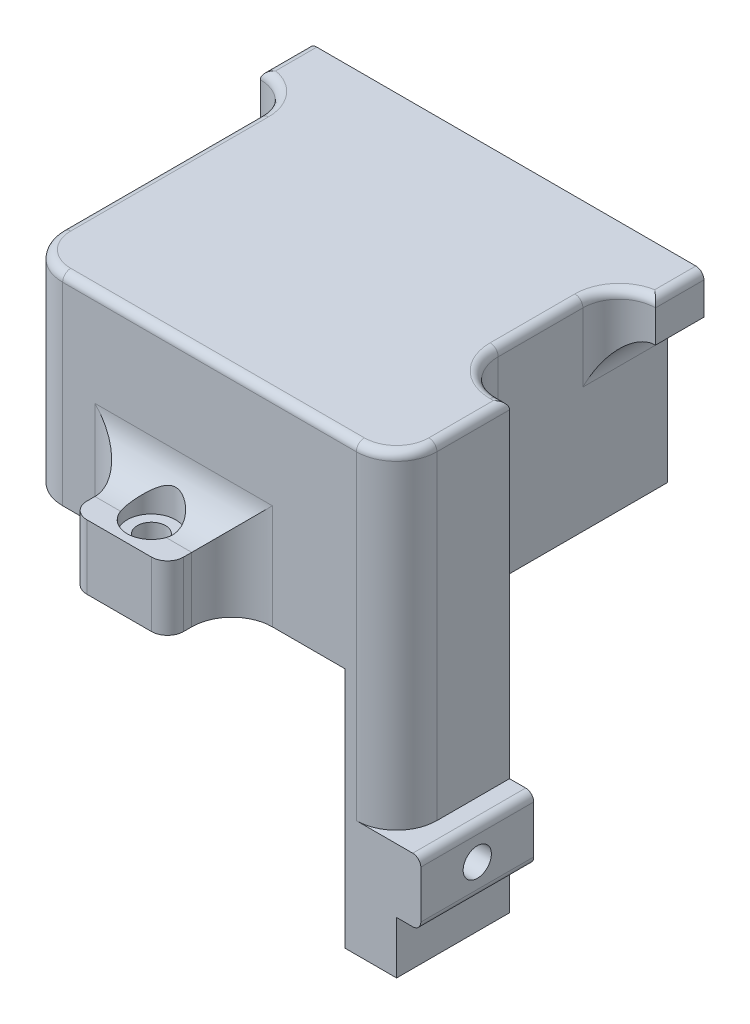
SolidWorks part; units mm, degrees
ref_plane "Alzado" through (0, 0, 0) normal (0, 0, 1) x (1, 0, 0)
ref_plane "Planta" through (0, 0, 0) normal (0, 1, 0) x (1, 0, 0)
ref_plane "Vista lateral" through (0, 0, 0) normal (1, 0, 0) x (0, 0, -1)
sketch "Croquis1" plane through (0, 0, 0) normal (0, 1, 0) x (1, 0, 0)
  line L1 (0, 0) -> (40, 0)
  line L2 (0, 0) -> (0, -40)
  line L3 (0, -40) -> (40, -40)
  line L4 (40, 0) -> (40, -40)
  dimension "D1" = 40
  dimension "D2" = 40
extrude "Saliente-Extruir1" add sketch "Croquis1" along normal blind 25
sketch "Croquis3" plane through (0, 0, 0) normal (0, 0, -1) x (-1, 0, 0)
  line L0 (0, 0) -> (-40, 25) construction
  line L1 (-40, 25) -> (0, 25) construction
  line L2 (-40, 25) -> (-40, 0) construction
  line L4 (-5, 21.5) -> (-35, 21.5)
  line L5 (-5, 21.5) -> (-5, 3.5)
  line L6 (-5, 3.5) -> (-35, 3.5)
  line L7 (-35, 21.5) -> (-35, 3.5)
  line L8 (-5, 21.5) -> (-35, 3.5) construction
  line L9 (-5, 3.5) -> (-35, 21.5) construction
  point P7 (-20, 12.5)
  dimension "D1" = 30
  dimension "D2" = 18
extrude "Cortar-Extruir1" cut sketch "Croquis3" against normal blind 30
sketch "Croquis4" plane through (0, 25, 0) normal (0, 1, 0) x (1, 0, 0)
  line L0 (40, -40) -> (40, 0) construction
  line L1 (35.5, 4) -> (44.5, 4)
  line L2 (35.5, 4) -> (35.5, -6)
  line L3 (35.5, -6) -> (44.5, -6)
  line L4 (44.5, 4) -> (44.5, -6)
  line L5 (4.5, 4) -> (-4.5, 4)
  line L6 (4.5, 4) -> (4.5, -6)
  line L7 (4.5, -6) -> (-4.5, -6)
  line L8 (-4.5, 4) -> (-4.5, -6)
  line L9 (40, 0) -> (0, 0) construction
  line L10 (0, 0) -> (0, -40) construction
  dimension "D1" = 9
  dimension "D2" = 4.5
  dimension "D3" = 10
  dimension "D4" = 4
  dimension "D5" = 9
  dimension "D6" = 10
  dimension "D7" = 4.5
  dimension "D8" = 4
extrude "Saliente-Extruir2" add sketch "Croquis4" against normal blind 5
fillet "Redondeo3" radius 4.5 4 edges at (0, 22.5, 6) (40, 22.5, 6) (0, 20, 3) (40, 20, 3)
sketch "Croquis8" plane through (0, 25, 0) normal (0, 1, 0) x (1, 0, 0)
  line L0 (40, -40) -> (40, -10.5) construction
  line L1 (40, -26) -> (46.4, -26)
  line L2 (40, -26) -> (40, -40)
  line L3 (40, -40) -> (46.4, -40)
  line L4 (46.4, -26) -> (46.4, -40)
  line L5 (0, -40) -> (40, -40) construction
  dimension "D1" = 6.4
  dimension "D2" = 14
extrude "Saliente-Extruir5" add sketch "Croquis8" against normal blind 55
sketch "Croquis9" plane through (46.4, 0, 0) normal (1, 0, 0) x (0, 0, -1)
  line L0 (-26, -30) -> (-26, 25) construction
  line L1 (-26, -15.6) -> (-40, -15.6)
  line L2 (-26, -15.6) -> (-26, -23.5)
  line L3 (-26, -23.5) -> (-40, -23.5)
  line L4 (-40, -15.6) -> (-40, -23.5)
  line L5 (-40, -30) -> (-40, 25) construction
  line L6 (-40, -30) -> (-26, -30) construction
  dimension "D1" = 7.9
  dimension "D2" = 6.5
extrude "Saliente-Extruir6" add sketch "Croquis9" along normal blind 3
sketch "Croquis10" plane through (0, 0, 0) normal (0, -1, 0) x (1, 0, 0)
  line L5 (20, 0) -> (20, 40) construction
  line L6 (0, 10.5) -> (-8, 10.5)
  line L7 (0, 10.5) -> (0, 22.5)
  line L8 (0, 22.5) -> (-8, 22.5)
  line L9 (-8, 10.5) -> (-8, 22.5)
  line L10 (40, 0) -> (0, 0) construction
  line L11 (0, 40) -> (40, 40) construction
  line L13 (26, 40) -> (14, 40)
  line L14 (26, 40) -> (26, 48)
  line L15 (26, 48) -> (14, 48)
  line L16 (14, 40) -> (14, 48)
  dimension "D1" = 12
  dimension "D2" = 8
  dimension "D3" = 12
  dimension "D4" = 8
  dimension "D5" = 6
extrude "Saliente-Extruir7" add sketch "Croquis10" against normal blind 8
sketch "Croquis11" plane through (0, 0, 0) normal (0, -1, 0) x (1, 0, 0)
  line L0 (-8, 16.5) -> (0.4912, 16.5) construction
  line L1 (-8, 22.5) -> (-8, 10.5) construction
  line L2 (-4, 10.5) -> (-4, 22.5) construction
  line L5 (26, 44) -> (14, 44) construction
  line L6 (26, 40) -> (26, 48) construction
  line L7 (14, 48) -> (14, 40) construction
  line L8 (20, 48) -> (20, 39.7958) construction
  line L9 (26, 48) -> (14, 48) construction
  line L10 (-8, 10.5) -> (0, 10.5) construction
  line L11 (0, 22.5) -> (-8, 22.5) construction
  circle A0 centre (20, 44) radius 1.75
  circle A1 centre (-4, 16.5) radius 1.75
  dimension "D1" = 3.5
  dimension "D2" = 3.5
extrude "Cortar-Extruir2" cut sketch "Croquis11" against normal up to surface (8 mm away) up to face at (-4, 8, 16.5)
sketch "Croquis12" plane through (0, 8, 0) normal (0, 1, 0) x (1, 0, 0)
  circle A0 centre (20, -44) radius 3
  circle A1 centre (-4, -16.5) radius 3
  dimension "D1" = 6
  dimension "D2" = 6
extrude "Cortar-Extruir3" cut sketch "Croquis12" against normal blind 1.5
fillet "Redondeo5" radius 1 2 edges at (49.4, -15.6, 33) (49.4, -23.5, 33)
sketch "Croquis13" plane through (49.4, 0, 0) normal (1, 0, 0) x (0, 0, -1)
  line L0 (-26, -19.55) -> (-40, -19.55) construction
  line L1 (-26, -22.5) -> (-26, -16.6) construction
  line L2 (-40, -16.6) -> (-40, -22.5) construction
  circle A0 centre (-33, -19.55) radius 1.75
  dimension "D1" = 3.5
extrude "Cortar-Extruir4" cut sketch "Croquis13" against normal up to surface (9.4 mm away) up to face at (40, -15, 33)
sketch "Croquis14" plane through (40, 0, 0) normal (-1, 0, 0) x (0, 0, 1)
  circle A0 centre (33, -19.55) radius 3
  dimension "D1" = 6
extrude "Cortar-Extruir5" cut sketch "Croquis14" against normal blind 1.5
fillet "Redondeo4" radius 5 9 edges at (40, 12.5, 26) (46.4, 4.7, 40) (26, 4, 40) (14, 4, 40) (20, 8, 40) (0, 8, 16.5) (0, 4, 22.5) (0, 4, 10.5) (0, 12.5, 40)
fillet "Redondeo6" radius 1 12 edges at (45.7, 25, 26) (41.318, 25, 7.318) (40, 25, 15.75) (-1.318, 25, 7.318) (46.4, 25, 30.5) (44.9355, 25, 38.5355) (23.2, 25, 40) (1.4645, 25, 38.5355) (44.5, 25, 1) (41.4645, 25, 24.5355) (0, 25, 22.75) (-4.5, 25, 1)
fillet "Redondeo7" radius 2 4 edges at (-8, 4, 10.5) (-8, 4, 22.5) (14, 4, 48) (26, 4, 48)
sketch "Croquis15" plane through (0, 20, 0) normal (0, -1, 0) x (1, 0, 0)
  line L4 (4.5, 0) -> (-4.5, 0)
  line L5 (-4.5, 0) -> (-4.5, -4)
  line L6 (-4.5, -4) -> (4.5, -4)
  line L7 (4.5, -4) -> (4.5, 0)
  line L8 (4.5, 0) -> (-4.5, 0)
  line L9 (-4.5, 0) -> (-4.5, -4)
  line L10 (-4.5, -4) -> (4.5, -4)
  line L11 (4.5, -4) -> (4.5, 0)
  line L12 (44.5, -4) -> (44.5, 0)
  line L13 (44.5, 0) -> (35.5, 0)
  line L14 (35.5, 0) -> (35.5, -4)
  line L15 (35.5, -4) -> (44.5, -4)
  line L16 (44.5, -4) -> (44.5, 0)
  line L17 (44.5, 0) -> (35.5, 0)
  line L18 (35.5, 0) -> (35.5, -4)
  line L19 (35.5, -4) -> (44.5, -4)
  dimension "D1" = 0
  dimension "D2" = 0
extrude "Cortar-Extruir6" cut sketch "Croquis15" against normal through all
